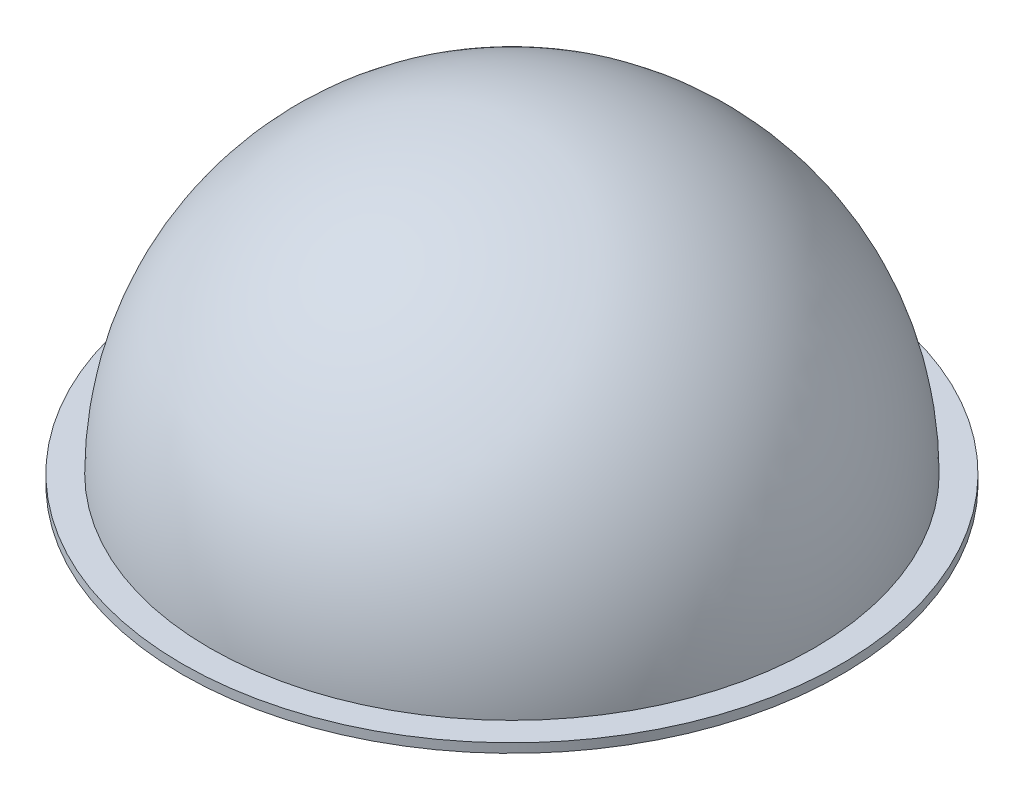
SolidWorks part; units mm, degrees
ref_plane "Front Plane" through (0, 0, 0) normal (0, 0, 1) x (1, 0, 0)
ref_plane "Top Plane" through (0, 0, 0) normal (0, 1, 0) x (1, 0, 0)
ref_plane "Right Plane" through (0, 0, 0) normal (1, 0, 0) x (0, 0, -1)
sketch "Sketch1" plane through (0, 0, 0) normal (0, 0, 1) x (1, 0, 0)
  line L0 (49.5, 0) -> (48, 0) construction
  line L1 (0, 49.5) -> (0, 48)
  line L2 (48, 0) -> (48, -1.5)
  line L3 (48, -1.5) -> (54, -1.5)
  line L4 (54, -1.5) -> (54, 0)
  line L5 (54, 0) -> (49.5, 0)
  line L6 (0, 0) -> (0, 44.5184) construction
  arc A0 (49.5, 0) -> (0, 49.5) centre (0, 0) ccw
  arc A1 (48, 0) -> (0, 48) centre (0, 0) ccw
  dimension "D1" = 49.5
  dimension "D2" = 1.5
  dimension "D4" = 1.5
  dimension "D5" = 6
revolve "Revolve1" add sketch "Sketch1" angle 360 about L1
